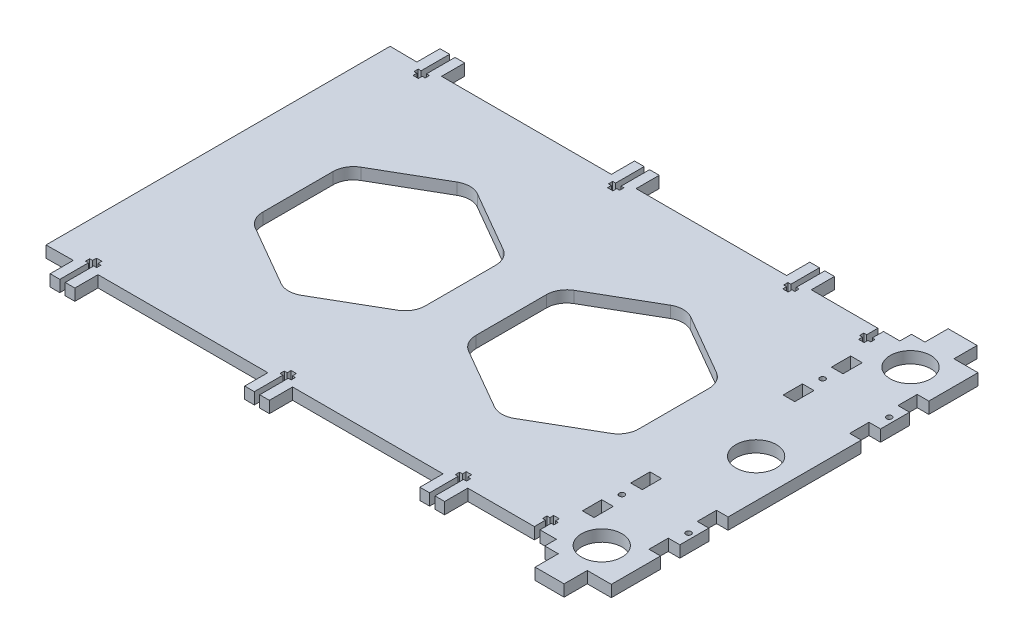
SolidWorks part; units mm, degrees
ref_plane "Спереди" through (0, 0, 0) normal (0, 0, 1) x (1, 0, 0)
ref_plane "Сверху" through (0, 0, 0) normal (0, 1, 0) x (1, 0, 0)
ref_plane "Справа" through (0, 0, 0) normal (1, 0, 0) x (0, 0, -1)
sketch "Эскиз1" plane through (0, 0, 0) normal (0, 1, 0) x (1, 0, 0)
  line L32 (-23.9169, 26.9382) -> (-55.4959, 45.1703)
  line L33 (-66.0222, 45.1703) -> (-97.6012, 26.9382)
  line L34 (-102.8643, 17.8222) -> (-102.8643, -0.4099)
  line L37 (-18.6538, -18.6421) -> (-18.6538, 17.8222)
  line L40 (91.8726, -0.4099) -> (91.8726, 17.8222)
  line L41 (86.6094, 26.9382) -> (55.0304, 45.1703)
  line L42 (44.5041, 45.1703) -> (12.9252, 26.9382)
  line L43 (7.662, 17.8222) -> (7.662, -18.6421)
  line L188 (154.5041, 128.5638) -> (154.5041, -125.2674) construction
  line L189 (175.6449, -0.4099) -> (-201.3479, -0.4099) construction
  line L190 (169.6988, 94.5901) -> (-201.3479, 94.5901) construction
  line L191 (168.2514, -95.4099) -> (-202.7953, -95.4099) construction
  line L192 (169.6988, 106.5901) -> (89.704, 106.5901) construction
  line L193 (-117.4736, -101.4099) -> (-117.4736, -89.4099)
  line L194 (108.4192, -125.2328) -> (108.4192, 116.6247) construction
  line L195 (134.5357, 79.5901) -> (134.5357, 90.0901) construction
  line L196 (134.5357, 128.5638) -> (134.5357, -125.2674) construction
  line L197 (148.5041, 128.5638) -> (148.5041, -125.2674) construction
  line L198 (169.6988, 69.0901) -> (102.787, 69.0901) construction
  line L200 (169.6988, 59.0901) -> (102.787, 59.0901) construction
  line L201 (102.787, 44.0901) -> (169.6988, 44.0901) construction
  line L202 (102.787, 34.0901) -> (169.6988, 34.0901) construction
  line L203 (-122.4736, -101.4099) -> (-117.4736, -101.4099)
  line L204 (-130.2736, -101.4099) -> (-130.2736, -89.4099)
  line L205 (-125.2736, -101.4099) -> (-130.2736, -101.4099)
  line L206 (-126.7736, -86.6099) -> (-125.2736, -86.6099)
  line L207 (154.5041, 69.0901) -> (148.5041, 69.0901)
  line L208 (148.5041, 69.0901) -> (148.5041, 59.0901)
  line L209 (148.5041, 59.0901) -> (154.5041, 59.0901)
  line L210 (154.5041, 44.0901) -> (148.5041, 44.0901)
  line L211 (148.5041, 44.0901) -> (148.5041, 34.0901)
  line L212 (148.5041, 34.0901) -> (154.5041, 34.0901)
  line L213 (151.5041, 128.5638) -> (151.5041, -125.2674) construction
  line L214 (169.6988, 51.5901) -> (102.787, 51.5901) construction
  line L215 (-126.7736, -84.4099) -> (-126.7736, -86.6099)
  line L223 (154.5041, -34.9099) -> (154.5041, 34.0901)
  line L224 (154.5041, 44.0901) -> (154.5041, 59.0901)
  line L225 (154.5041, 69.0901) -> (154.5041, 94.5901)
  line L227 (142.0357, 94.5901) -> (142.0357, 106.5901)
  line L228 (142.0357, 106.5901) -> (127.0357, 106.5901)
  line L229 (127.0357, 106.5901) -> (127.0357, 94.5901)
  line L230 (142.0357, 94.5901) -> (154.5041, 94.5901)
  line L231 (124.0357, 116.5901) -> (124.0357, -125.2674) construction
  line L232 (120.0357, 116.5901) -> (120.0357, -125.2674) construction
  line L233 (114.0357, 116.5901) -> (114.0357, -125.2674) construction
  line L234 (169.6988, 88.5901) -> (114.0357, 88.5901) construction
  line L235 (120.0357, 94.5901) -> (120.0357, 88.5901)
  line L236 (120.0357, 94.5901) -> (127.0357, 94.5901)
  line L237 (120.0357, 88.5901) -> (111.5357, 88.5901)
  line L238 (-24.4736, 100.5895) -> (-24.4736, 85.7895)
  line L239 (116.9781, 116.5901) -> (116.9781, -125.2674) construction
  line L240 (114.0357, 69.0901) -> (120.0357, 69.0901)
  line L241 (114.0357, 69.0901) -> (114.0357, 59.0901)
  line L242 (114.0357, 59.0901) -> (120.0357, 59.0901)
  line L243 (120.0357, 69.0901) -> (120.0357, 59.0901)
  line L244 (114.0357, 44.0901) -> (120.0357, 44.0901)
  line L245 (114.0357, 44.0901) -> (114.0357, 34.0901)
  line L246 (114.0357, 34.0901) -> (120.0357, 34.0901)
  line L247 (120.0357, 44.0901) -> (120.0357, 34.0901)
  line L248 (-125.2736, -84.4099) -> (-126.7736, -84.4099)
  line L257 (-125.2736, -82.4099) -> (-125.2736, -84.4099)
  line L258 (-122.4736, -82.4099) -> (-125.2736, -82.4099)
  line L259 (-122.4736, -84.4099) -> (-122.4736, -82.4099)
  line L260 (-120.9736, -84.4099) -> (-122.4736, -84.4099)
  line L261 (-120.9736, -86.6099) -> (-120.9736, -84.4099)
  line L262 (-122.4736, -86.6099) -> (-120.9736, -86.6099)
  line L263 (-130.2736, -89.4099) -> (-144.2736, -89.5669)
  line L264 (-16.6736, -101.4094) -> (-16.6736, -89.4099)
  line L265 (112.9264, 107.7365) -> (112.9264, -92.2635) construction
  line L266 (111.5357, 107.7365) -> (111.5357, -92.2635) construction
  line L267 (108.6264, 107.7365) -> (108.6264, -92.2635) construction
  line L268 (107.1264, 107.7365) -> (107.1264, -92.2635) construction
  line L269 (-21.6736, -101.4094) -> (-16.6736, -101.4094)
  line L270 (127.0357, -95.4099) -> (120.0357, -95.4099)
  line L271 (-29.4736, -101.4094) -> (-29.4736, -89.4094)
  line L272 (-24.4736, -101.4094) -> (-29.4736, -101.4094)
  line L273 (-117.4736, -89.4099) -> (-29.4736, -89.4094)
  line L274 (-21.6736, -86.6094) -> (-21.6736, -101.4094)
  line L275 (-25.9736, -86.6094) -> (-24.4736, -86.6094)
  line L276 (-25.9736, -84.4094) -> (-25.9736, -86.6094)
  line L277 (-24.4736, -84.4094) -> (-25.9736, -84.4094)
  line L278 (-24.4736, -82.4094) -> (-24.4736, -84.4094)
  line L279 (-21.6736, -82.4094) -> (-24.4736, -82.4094)
  line L280 (-21.6736, -84.4094) -> (-21.6736, -82.4094)
  line L281 (-20.1736, -84.4094) -> (-21.6736, -84.4094)
  line L282 (121.9861, 78.5901) -> (101.737, 78.5901) construction
  line L283 (121.9861, 80.5901) -> (101.737, 80.5901) construction
  line L284 (121.9861, 82.7901) -> (101.737, 82.7901) construction
  line L285 (111.5357, 88.5901) -> (111.5357, 82.7901)
  line L286 (111.5357, 82.7901) -> (112.9264, 82.7901)
  line L287 (112.9264, 82.7901) -> (112.9264, 80.5901)
  line L288 (112.9264, 80.5901) -> (111.5357, 80.5901)
  line L289 (111.5357, 80.5901) -> (111.5357, 78.5901)
  line L290 (111.5357, 78.5901) -> (108.6264, 78.5901)
  line L291 (108.6264, 78.5901) -> (108.6264, 80.5901)
  line L292 (108.6264, 80.5901) -> (107.1264, 80.5901)
  line L293 (107.1264, 80.5901) -> (107.1264, 82.7901)
  line L294 (107.1264, 82.7901) -> (108.6264, 82.7901)
  line L295 (108.6264, 82.7901) -> (108.6264, 88.5901)
  line L296 (108.6264, 88.5901) -> (74.1264, 88.5901)
  line L297 (169.6988, 100.5901) -> (-201.3479, 100.5901) construction
  line L298 (70.6264, 45.1703) -> (70.6264, 137.9979) construction
  line L299 (-23.0736, 45.1703) -> (-23.0736, 137.9979) construction
  line L300 (-123.8736, 137.9979) -> (-123.8736, 45.1703) construction
  line L301 (75.3218, 85.7901) -> (58.936, 85.7901) construction
  line L302 (75.3218, 83.5901) -> (58.936, 83.5901) construction
  line L303 (75.3218, 81.5901) -> (58.936, 81.5901) construction
  line L304 (69.1264, 137.9979) -> (69.1264, 45.1703) construction
  line L305 (66.3264, 137.819) -> (66.3264, 44.9915) construction
  line L306 (64.8264, 137.819) -> (64.8264, 44.9915) construction
  line L307 (66.3264, 100.5901) -> (66.3264, 85.7901)
  line L308 (69.1264, 85.7901) -> (70.6264, 85.7901)
  line L309 (70.6264, 85.7901) -> (70.6264, 83.5901)
  line L310 (70.6264, 83.5901) -> (69.1264, 83.5901)
  line L311 (69.1264, 83.5901) -> (69.1264, 81.5901)
  line L312 (69.1264, 81.5901) -> (66.3264, 81.5901)
  line L313 (66.3264, 81.5901) -> (66.3264, 83.5901)
  line L314 (66.3264, 83.5901) -> (64.8264, 83.5901)
  line L315 (64.8264, 83.5901) -> (64.8264, 85.7901)
  line L316 (64.8264, 85.7901) -> (66.3264, 85.7901)
  line L317 (69.1264, 100.5901) -> (69.1264, 85.7901)
  line L318 (-125.2736, 100.5901) -> (-125.2736, 85.7901)
  line L319 (66.3264, 100.5901) -> (61.3264, 100.5901)
  line L320 (61.3264, 100.5901) -> (61.3264, 88.5901)
  line L321 (-122.4736, 100.5901) -> (-122.4736, 85.7901)
  line L322 (69.1264, 100.5901) -> (74.1264, 100.5901)
  line L323 (74.1264, 100.5901) -> (74.1264, 88.5901)
  line L324 (61.3264, 88.5901) -> (-16.6736, 88.5901)
  line L325 (-21.6736, 85.7895) -> (-20.1736, 85.7895)
  line L326 (-20.1736, 85.7895) -> (-20.1736, 83.5895)
  line L327 (-20.1736, 83.5895) -> (-21.6736, 83.5895)
  line L328 (-21.6736, 83.5895) -> (-21.6736, 81.5895)
  line L329 (-21.6736, 81.5895) -> (-24.4736, 81.5895)
  line L330 (-24.4736, 81.5895) -> (-24.4736, 83.5895)
  line L331 (-24.4736, 83.5895) -> (-25.9736, 83.5895)
  line L332 (-25.9736, 83.5895) -> (-25.9736, 85.7895)
  line L333 (-25.9736, 85.7895) -> (-24.4736, 85.7895)
  line L334 (-21.6736, 85.7895) -> (-21.6736, 100.5895)
  line L335 (-117.4736, 88.5901) -> (-29.4736, 88.5895)
  line L336 (-24.4736, 100.5895) -> (-29.4736, 100.5895)
  line L337 (-29.4736, 100.5895) -> (-29.4736, 88.5895)
  line L338 (-144.2736, 137.9979) -> (-144.2736, 39.4961) construction
  line L339 (-21.6736, 100.5895) -> (-16.6736, 100.5895)
  line L340 (-16.6736, 100.5895) -> (-16.6736, 88.5901)
  line L341 (-130.2736, 88.5901) -> (-144.2736, 88.747)
  line L343 (-122.4736, 85.7901) -> (-120.9736, 85.7901)
  line L344 (-120.9736, 85.7901) -> (-120.9736, 83.5901)
  line L345 (-120.9736, 83.5901) -> (-122.4736, 83.5901)
  line L346 (-122.4736, 83.5901) -> (-122.4736, 81.5901)
  line L347 (-122.4736, 81.5901) -> (-125.2736, 81.5901)
  line L348 (-125.2736, 81.5901) -> (-125.2736, 83.5901)
  line L349 (-125.2736, 83.5901) -> (-126.7736, 83.5901)
  line L350 (-126.7736, 83.5901) -> (-126.7736, 85.7901)
  line L351 (-126.7736, 85.7901) -> (-125.2736, 85.7901)
  line L352 (-20.1736, -86.6094) -> (-20.1736, -84.4094)
  line L353 (-21.6736, -86.6094) -> (-20.1736, -86.6094)
  line L354 (-125.2736, 100.5901) -> (-130.2736, 100.5901)
  line L355 (-130.2736, 100.5901) -> (-130.2736, 88.5901)
  line L356 (61.3264, -89.4099) -> (-16.6736, -89.4099)
  line L357 (-122.4736, 100.5901) -> (-117.4736, 100.5901)
  line L358 (-117.4736, 100.5901) -> (-117.4736, 88.5901)
  line L359 (74.1264, -101.4099) -> (74.1264, -89.4099)
  line L360 (69.1264, -101.4099) -> (74.1264, -101.4099)
  line L361 (-122.4736, -101.4099) -> (-122.4736, -86.6099)
  line L362 (61.3264, -101.4099) -> (61.3264, -89.4099)
  line L363 (66.3264, -101.4099) -> (61.3264, -101.4099)
  line L364 (-125.2736, -101.4099) -> (-125.2736, -86.6099)
  line L365 (69.1264, -101.4099) -> (69.1264, -86.6099)
  line L366 (64.8264, -86.6099) -> (66.3264, -86.6099)
  line L367 (64.8264, -84.4099) -> (64.8264, -86.6099)
  line L368 (66.3264, -84.4099) -> (64.8264, -84.4099)
  line L369 (66.3264, -82.4099) -> (66.3264, -84.4099)
  line L370 (69.1264, -82.4099) -> (66.3264, -82.4099)
  line L371 (69.1264, -84.4099) -> (69.1264, -82.4099)
  line L372 (70.6264, -84.4099) -> (69.1264, -84.4099)
  line L373 (70.6264, -86.6099) -> (70.6264, -84.4099)
  line L374 (69.1264, -86.6099) -> (70.6264, -86.6099)
  line L375 (66.3264, -101.4099) -> (66.3264, -86.6099)
  line L376 (-144.2736, 88.747) -> (-144.2736, -89.5669)
  line L385 (108.6264, -89.4099) -> (74.1264, -89.4099)
  line L386 (108.6264, -83.6099) -> (108.6264, -89.4099)
  line L387 (107.1264, -83.6099) -> (108.6264, -83.6099)
  line L388 (107.1264, -81.4099) -> (107.1264, -83.6099)
  line L389 (108.6264, -81.4099) -> (107.1264, -81.4099)
  line L390 (108.6264, -79.4099) -> (108.6264, -81.4099)
  line L391 (111.5357, -79.4099) -> (108.6264, -79.4099)
  line L392 (111.5357, -81.4099) -> (111.5357, -79.4099)
  line L393 (112.9264, -81.4099) -> (111.5357, -81.4099)
  line L394 (112.9264, -83.6099) -> (112.9264, -81.4099)
  line L395 (111.5357, -83.6099) -> (112.9264, -83.6099)
  line L396 (111.5357, -89.4099) -> (111.5357, -83.6099)
  line L400 (120.0357, -44.9099) -> (120.0357, -34.9099)
  line L401 (114.0357, -34.9099) -> (120.0357, -34.9099)
  line L402 (114.0357, -44.9099) -> (114.0357, -34.9099)
  line L403 (114.0357, -44.9099) -> (120.0357, -44.9099)
  line L404 (120.0357, -69.9099) -> (120.0357, -59.9099)
  line L405 (114.0357, -59.9099) -> (120.0357, -59.9099)
  line L406 (114.0357, -69.9099) -> (114.0357, -59.9099)
  line L407 (114.0357, -69.9099) -> (120.0357, -69.9099)
  line L408 (-24.4736, -101.4094) -> (-24.4736, -86.6094)
  line L409 (120.0357, -89.4099) -> (111.5357, -89.4099)
  line L411 (120.0357, -95.4099) -> (120.0357, -89.4099)
  line L413 (142.0357, -95.4099) -> (154.5041, -95.4099)
  line L414 (127.0357, -107.4099) -> (127.0357, -95.4099)
  line L415 (142.0357, -107.4099) -> (127.0357, -107.4099)
  line L416 (142.0357, -95.4099) -> (142.0357, -107.4099)
  line L417 (154.5041, -69.9099) -> (154.5041, -95.4099)
  line L418 (154.5041, -44.9099) -> (154.5041, -59.9099)
  line L420 (148.5041, -34.9099) -> (154.5041, -34.9099)
  line L421 (148.5041, -44.9099) -> (148.5041, -34.9099)
  line L422 (154.5041, -44.9099) -> (148.5041, -44.9099)
  line L423 (148.5041, -59.9099) -> (154.5041, -59.9099)
  line L424 (148.5041, -69.9099) -> (148.5041, -59.9099)
  line L425 (154.5041, -69.9099) -> (148.5041, -69.9099)
  line L433 (44.5041, -45.9902) -> (12.9252, -27.7581)
  line L434 (86.6094, -27.7581) -> (55.0304, -45.9902)
  line L435 (91.8726, -0.4099) -> (91.8726, -18.6421)
  line L436 (-102.8643, -18.6421) -> (-102.8643, -0.4099)
  line L437 (-66.0222, -45.9902) -> (-97.6012, -27.7581)
  line L438 (-23.9169, -27.7581) -> (-55.4959, -45.9902)
  circle A3 centre (134.5357, 79.5901) radius 10.5
  circle A14 centre (134.5357, -0.4099) radius 10.5
  arc A15 (-18.6538, 17.8222) -> (-23.9169, 26.9382) centre (-29.1801, 17.8222) ccw
  arc A16 (-55.4959, 45.1703) -> (-66.0222, 45.1703) centre (-60.7591, 36.0543) ccw
  arc A17 (-97.6012, 26.9382) -> (-102.8643, 17.8222) centre (-92.338, 17.8222) ccw
  arc A24 (91.8726, 17.8222) -> (86.6094, 26.9382) centre (81.3462, 17.8222) ccw
  arc A25 (55.0304, 45.1703) -> (44.5041, 45.1703) centre (49.7673, 36.0543) ccw
  arc A26 (12.9252, 26.9382) -> (7.662, 17.8222) centre (18.1883, 17.8222) ccw
  circle A31 centre (151.5041, 51.5901) radius 1.4
  circle A33 centre (116.9781, 51.5901) radius 1.4
  circle A35 centre (116.9781, -52.4099) radius 1.4
  circle A36 centre (151.5041, -52.4099) radius 1.4
  arc A37 (12.9252, -27.7581) -> (7.662, -18.6421) centre (18.1883, -18.6421) cw
  arc A38 (55.0304, -45.9902) -> (44.5041, -45.9902) centre (49.7673, -36.8742) cw
  arc A39 (91.8726, -18.6421) -> (86.6094, -27.7581) centre (81.3462, -18.6421) cw
  arc A40 (-97.6012, -27.7581) -> (-102.8643, -18.6421) centre (-92.338, -18.6421) cw
  arc A41 (-55.4959, -45.9902) -> (-66.0222, -45.9902) centre (-60.7591, -36.8742) cw
  arc A42 (-18.6538, -18.6421) -> (-23.9169, -27.7581) centre (-29.1801, -18.6421) cw
  circle A43 centre (134.5357, -80.4099) radius 10.5
  point P11 (0, 0)
  point P26 (-18.6538, -0.4099)
  point P111 (-144.2736, -0.4099)
  point P228 (154.5041, -0.4099)
  point P246 (7.662, -0.4099)
  point P314 (-123.8736, 81.5901)
  point P326 (-23.0736, 81.5895)
  dimension "D1" = 21
  dimension "D4" = 80
  dimension "D6" = 95
  dimension "D19" = 2.8
  dimension "D24" = 4
  dimension "D27" = 2.8
  dimension "D8" = 12
  dimension "D11" = 10
  dimension "D12" = 10
  dimension "D13" = 15
  dimension "D17" = 3
  dimension "D18" = 7.5
  dimension "D22" = 7.5
  dimension "D23" = 15
  dimension "D25" = 6
  dimension "D26" = 6
  dimension "D32" = 12
  dimension "D33" = 38
  dimension "D34" = 1.5
  dimension "D35" = 2.8
  dimension "D36" = 1.5
  dimension "D37" = 7
  dimension "D38" = 2
  dimension "D39" = 2.2
  dimension "D40" = 5
  dimension "D41" = 5
  dimension "D42" = 5
  dimension "D43" = 2.8
  dimension "D44" = 5
  dimension "D45" = 88
  dimension "D46" = 78
  dimension "D47" = 100.8
  dimension "D48" = 84.4
  dimension "D49" = 5
  dimension "D50" = 2.8
  dimension "D51" = 5
  dimension "D52" = 14
extrude "Бобышка-Вытянуть1" add sketch "Эскиз1" along normal blind 6
